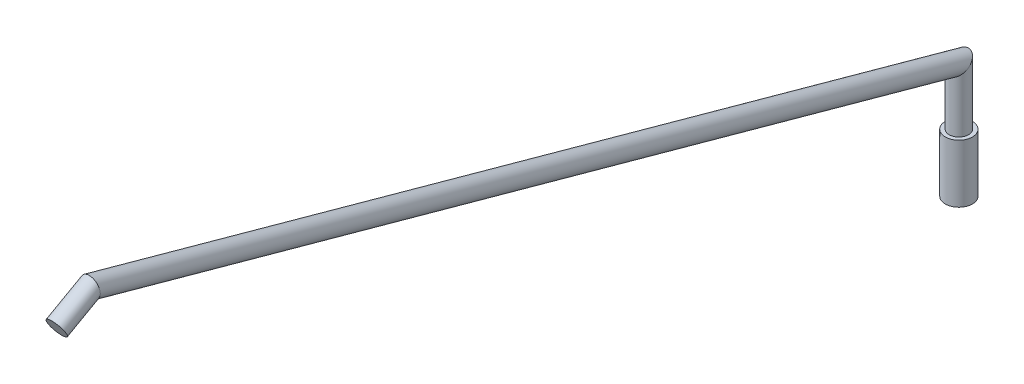
SolidWorks part; units mm, degrees
ref_plane "Front Plane" through (0, 0, 0) normal (0, 0, 1) x (1, 0, 0)
ref_plane "Top Plane" through (0, 0, 0) normal (0, 1, 0) x (1, 0, 0)
ref_plane "Right Plane" through (0, 0, 0) normal (1, 0, 0) x (0, 0, -1)
sketch "Sketch1" plane through (0, 0, 0) normal (1, 0, 0) x (0, 0, -1)
  line L0 (0, 0) -> (0, 30)
  line L1 (0, 30) -> (-224.2774, 91.8904)
  line L2 (-224.2774, 91.8904) -> (-233, 87)
  point P3 (0, 0)
  point P6 (0, 0)
  dimension "D1" = 233
  dimension "D2" = 87
  dimension "D3" = 30
  dimension "D4" = 10
ref_plane "Plane1" through (0, 87, 233) normal (0, -0.489, 0.8723) x (1, 0, 0)
sketch "Sketch2" plane through (0, 87, 233) normal (0, -0.489, 0.8723) x (1, 0, 0)
  circle A2 centre (0, 0) radius 2.5
  dimension "D1" = 5
sweep "Sweep1" add profiles "Sketch2" path "Sketch1"
sketch "Sketch3" plane through (0, 0, 0) normal (0, -1, 0) x (1, 0, 0)
  circle A2 centre (0, 0) radius 3.5
  circle A3 centre (0, 0) radius 3.5
  dimension "D1" = 1
extrude "Boss-Extrude1" add sketch "Sketch3" against normal blind 15
ref_plane "Attach to Counter Plane" through (0, 0, 0) normal (0, -1, 0) x (-1, 0, 0)
